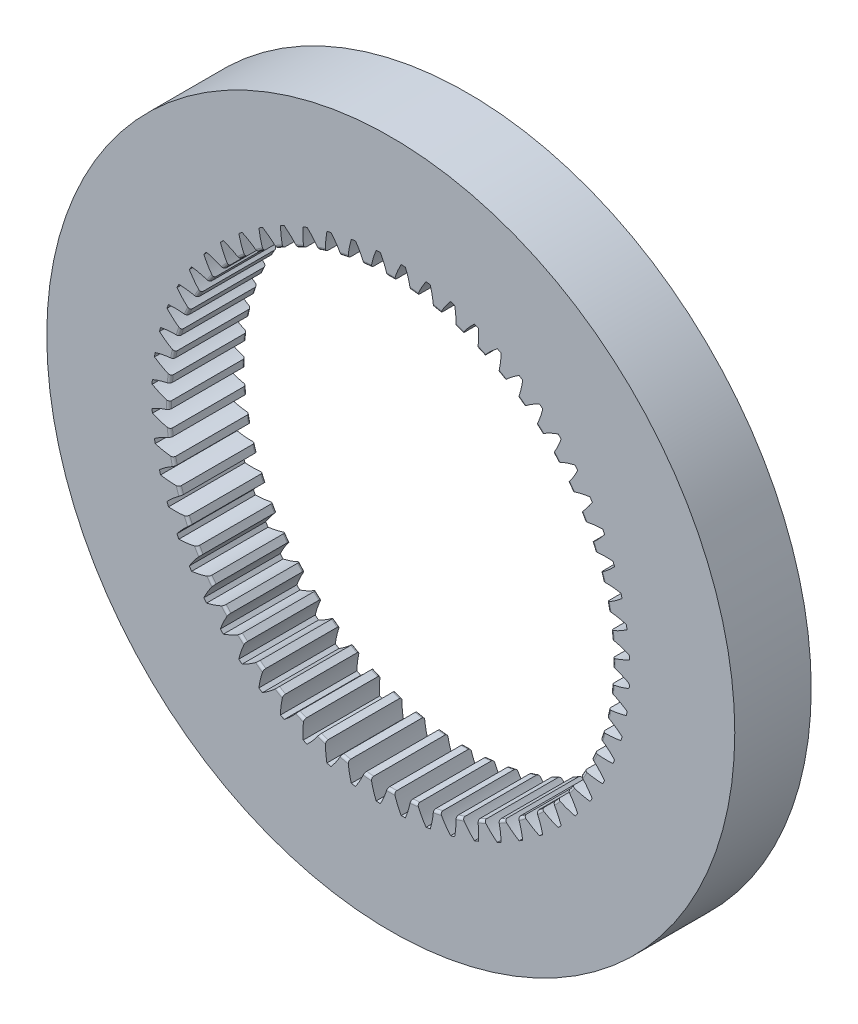
SolidWorks part; units mm, degrees
ref_plane "Front Plane" through (0, 0, 0) normal (0, 0, 1) x (1, 0, 0)
ref_plane "Top Plane" through (0, 0, 0) normal (0, 1, 0) x (1, 0, 0)
ref_plane "Right Plane" through (0, 0, 0) normal (1, 0, 0) x (0, 0, -1)
sketch "Sketch1" plane through (0, 0, 0) normal (0, 0, 1) x (1, 0, 0)
  line L0 (0, 0) -> (0, 30) construction
  line L1 (-9.6418, 33.5093) -> (9.6418, 26.4907) construction
  circle A0 centre (0, 0) radius 31 construction
  circle A1 centre (0, 0) radius 31.25 construction
  circle A2 centre (0, 0) radius 30 construction
  circle A3 centre (0, 0) radius 28.1908 construction
  circle A4 centre (0, 0) radius 45 construction
  circle A5 centre (0, 0) radius 29 construction
  point P8 (0.5, 0)
  point P13 (30, 0)
  dimension "Outside Diameter" = 62.5
  dimension "Root Diameter" = 62
  dimension "Gear Pitch Diameter" = 60
  dimension "ID | Base Diameter" = 56.3816
  dimension "OD" = 90
  dimension "ID" = 58
  dimension "Pressure Angle" = 20
  dimension "Number of Teeth" = 60
  dimension "Module" = 1
sketch "Sketch2" plane through (0, 0, 0) normal (1, 0, 0) x (0, 0, -1)
  line L0 (-5, 0) -> (5, 0) construction
  dimension "Face Width" = 10
sketch "Sketch3" plane through (0, 0, 0) normal (0, 0, 1) x (1, 0, 0)
  circle A0 centre (0, 0) radius 45
  circle A1 centre (0, 0) radius 29 construction
  circle A2 centre (0, 0) radius 29
  circle A4 centre (0, 0) radius 45 construction
extrude "Boss-Extrude1" add sketch "Sketch3" against normal up to vertex (5 mm away) and the other way up to vertex (5 mm away) up to point (0, 0, -5) other way up to point (0, 0, 5)
fillet "Fillet1" radius 0.3355 2 edges at (29, 0, -5) (29, 0, 5)
sketch "Sketch4" plane through (0, 0, 0) normal (0, 0, 1) x (1, 0, 0)
  line L2 (0, 0) -> (28.189, -0.3179) construction
  line L3 (0, 0) -> (28.189, 0.3179) construction
  line L4 (0, 0) -> (28.0678, -2.6304) construction
  circle A4 centre (0, 0) radius 28.1908 construction
  circle A5 centre (0, 0) radius 31.25 construction
  arc A7 (31.2205, -1.3573) -> (31.1914, -1.9136) centre (0, 0) cw
  arc A8 (28.189, -0.3179) -> (28.0678, -2.6304) centre (0, 0) cw
  spline S0 degree 4 poles (28.189, 0.3179) (28.1938, 0.318) (28.2071, 0.3184) (28.2324, 0.3198) (28.2736, 0.323) (28.3261, 0.3282) (28.3939, 0.3364) (28.4738, 0.3479) (28.5615, 0.3624) (28.6569, 0.3802) (28.7519, 0.3999) (28.8467, 0.4212) (28.941, 0.4439) (29.0552, 0.4733) (29.192, 0.511) (29.3517, 0.5588) (29.5326, 0.6173) (29.7167, 0.6815) (29.8976, 0.7486) (30.0801, 0.8207) (30.2564, 0.8936) (30.4393, 0.9739) (30.6079, 1.0502) (30.7965, 1.1408) (30.9486, 1.2153) (31.1487, 1.3189) (31.2668, 1.3817) (31.4048, 1.457) (31.4661, 1.4914) (31.5038, 1.5125) knots 0 0 0 0 0 0.005377 0.015084 0.028532 0.04661 0.064855 0.092111 0.119476 0.146842 0.174209 0.201575 0.228941 0.256307 0.307035 0.361767 0.4165 0.471232 0.525964 0.580697 0.635429 0.690161 0.744894 0.799626 0.854358 0.909091 0.954545 1 1 1 1 1 construction
  spline S1 degree 4 poles (28.189, 0.3179) (28.1938, 0.318) (28.2071, 0.3184) (28.2324, 0.3198) (28.2736, 0.323) (28.3261, 0.3282) (28.3939, 0.3364) (28.4738, 0.3479) (28.5615, 0.3624) (28.6569, 0.3802) (28.7519, 0.3999) (28.8467, 0.4212) (28.941, 0.4439) (29.0552, 0.4733) (29.192, 0.511) (29.3517, 0.5588) (29.5326, 0.6173) (29.7167, 0.6815) (29.8976, 0.7486) (30.0801, 0.8207) (30.2564, 0.8936) (30.4393, 0.9739) (30.6079, 1.0502) (30.7965, 1.1408) (30.9486, 1.2153) (31.1053, 1.2964) (31.1816, 1.3365) (31.2205, 1.3573) knots 0 0 0 0 0 0.005377 0.015084 0.028532 0.04661 0.064855 0.092111 0.119476 0.146842 0.174209 0.201575 0.228941 0.256307 0.307035 0.361767 0.4165 0.471232 0.525964 0.580697 0.635429 0.690161 0.744894 0.799626 0.854358 0.909091 0.909091 0.909091 0.909091 0.909091 construction
  spline S2 degree 4 poles (28.189, -0.3179) (28.1938, -0.318) (28.2071, -0.3184) (28.2324, -0.3198) (28.2736, -0.323) (28.3261, -0.3282) (28.3939, -0.3364) (28.4738, -0.3479) (28.5615, -0.3624) (28.6569, -0.3802) (28.7519, -0.3999) (28.8467, -0.4212) (28.941, -0.4439) (29.0552, -0.4733) (29.192, -0.511) (29.3517, -0.5588) (29.5326, -0.6173) (29.7167, -0.6815) (29.8976, -0.7486) (30.0801, -0.8207) (30.2564, -0.8936) (30.4393, -0.9739) (30.6079, -1.0502) (30.7965, -1.1408) (30.9486, -1.2153) (31.1487, -1.3189) (31.2668, -1.3817) (31.4048, -1.457) (31.4661, -1.4914) (31.5038, -1.5125) knots 0 0 0 0 0 0.005377 0.015084 0.028532 0.04661 0.064855 0.092111 0.119476 0.146842 0.174209 0.201575 0.228941 0.256307 0.307035 0.361767 0.4165 0.471232 0.525964 0.580697 0.635429 0.690161 0.744894 0.799626 0.854358 0.909091 0.954545 1 1 1 1 1 construction
  spline S3 degree 4 poles (28.189, -0.3179) (28.1938, -0.318) (28.2071, -0.3184) (28.2324, -0.3198) (28.2736, -0.323) (28.3261, -0.3282) (28.3939, -0.3364) (28.4738, -0.3479) (28.5615, -0.3624) (28.6569, -0.3802) (28.7519, -0.3999) (28.8467, -0.4212) (28.941, -0.4439) (29.0552, -0.4733) (29.192, -0.511) (29.3517, -0.5588) (29.5326, -0.6173) (29.7167, -0.6815) (29.8976, -0.7486) (30.0801, -0.8207) (30.2564, -0.8936) (30.4393, -0.9739) (30.6079, -1.0502) (30.7965, -1.1408) (30.9486, -1.2153) (31.1053, -1.2964) (31.1816, -1.3365) (31.2205, -1.3573) knots 0 0 0 0 0 0.005377 0.015084 0.028532 0.04661 0.064855 0.092111 0.119476 0.146842 0.174209 0.201575 0.228941 0.256307 0.307035 0.361767 0.4165 0.471232 0.525964 0.580697 0.635429 0.690161 0.744894 0.799626 0.854358 0.909091 0.909091 0.909091 0.909091 0.909091
  spline S4 degree 4 poles (28.0678, -2.6304) (28.0725, -2.6308) (28.0859, -2.6318) (28.1112, -2.633) (28.1525, -2.6342) (28.2052, -2.6345) (28.2736, -2.6334) (28.3542, -2.6304) (28.4429, -2.6251) (28.5396, -2.6173) (28.6362, -2.6077) (28.7327, -2.5964) (28.8289, -2.5837) (28.9455, -2.5664) (29.0855, -2.5432) (29.2493, -2.5124) (29.4354, -2.4731) (29.6251, -2.4284) (29.8121, -2.3807) (30.0011, -2.328) (30.1841, -2.2739) (30.3744, -2.2132) (30.5501, -2.1549) (30.747, -2.0846) (30.9061, -2.0264) (31.1159, -1.9443) (31.2399, -1.8942) (31.3851, -1.8337) (31.4496, -1.8059) (31.4893, -1.7888) knots 0 0 0 0 0 0.005377 0.015084 0.028532 0.04661 0.064855 0.092111 0.119476 0.146842 0.174209 0.201575 0.228941 0.256307 0.307035 0.361767 0.4165 0.471232 0.525964 0.580697 0.635429 0.690161 0.744894 0.799626 0.854358 0.909091 0.954545 1 1 1 1 1 construction
  spline S5 degree 4 poles (28.0678, -2.6304) (28.0725, -2.6308) (28.0859, -2.6318) (28.1112, -2.633) (28.1525, -2.6342) (28.2052, -2.6345) (28.2736, -2.6334) (28.3542, -2.6304) (28.4429, -2.6251) (28.5396, -2.6173) (28.6362, -2.6077) (28.7327, -2.5964) (28.8289, -2.5837) (28.9455, -2.5664) (29.0855, -2.5432) (29.2493, -2.5124) (29.4354, -2.4731) (29.6251, -2.4284) (29.8121, -2.3807) (30.0011, -2.328) (30.1841, -2.2739) (30.3744, -2.2132) (30.5501, -2.1549) (30.747, -2.0846) (30.9061, -2.0264) (31.0704, -1.9621) (31.1505, -1.9302) (31.1914, -1.9136) knots 0 0 0 0 0 0.005377 0.015084 0.028532 0.04661 0.064855 0.092111 0.119476 0.146842 0.174209 0.201575 0.228941 0.256307 0.307035 0.361767 0.4165 0.471232 0.525964 0.580697 0.635429 0.690161 0.744894 0.799626 0.854358 0.909091 0.909091 0.909091 0.909091 0.909091
  point P11 (0, 0)
  dimension "D1" = 6
extrude "Cut-Extrude1" cut sketch "Sketch4" against normal through all both and the other way through all
fillet "Fillet2" radius 0.3355 2 edges at (31.1914, -1.9136, 0) (31.2205, -1.3573, 0)
pattern_circular "CirPattern1" count 60 over 360 about axis through (0, 0, 5) along (0, 0, -1) of "Cut-Extrude1"
equation "\"Root Diameter@Sketch1\"=\"Root Diameter\""
equation "\"Outside Diameter@Sketch1\" = \"Outside Diameter\""
equation "\"D1@CirPattern1\"=\"Number of Teeth\""
equation "\"Diametral Pitch\"= 1 / \"Module\""
equation "\"Number of Teeth\"= 60"
equation "\"Pressure Angle\"=20"
equation "\"Pitch Diameter\"= \"Number of Teeth\" / \"Diametral Pitch\""
equation "\"Base Diameter\"= \"Pitch Diameter\" * cos ( \"Pressure Angle\" )"
equation "\"Outside Diameter\"= \"Pitch Diameter\" + ( 2 * \"Dedendum\" )"
equation "\"Dedendum\"= 1.25 / \"Diametral Pitch\""
equation "\"Root Diameter\"= \"Pitch Diameter\" + ( 2 * \"Addendum\" )"
equation "\"Pitch Angle\"= 360deg / \"Number of Teeth\""
equation "\"Alpha\"= sqr ( \"Pitch Diameter\" ^ 2 - \"Base Diameter\" ^ 2 ) / \"Base Diameter\" * 180 / PI - \"Pressure Angle\""
equation "\"Beta\"= ( \"Pitch Angle\" / 4 - \"Alpha\" )"
equation "\"Phi\"= sqr ( ( \"Outside Diameter\" / 2 ) ^ 2 - ( \"Base Diameter\" / 2 ) ^ 2 ) / ( \"Base Diameter\" / 2 )"
equation "\"Addendum\"= 1 / \"Diametral Pitch\""
equation "\"WorkingDepth\"= 2 / \"Diametral Pitch\""
equation "\"WholeDepth\"= 2.25 / \"Diametral Pitch\""
equation "\"Clearance\"= 0.25 / \"Diametral Pitch\""
equation "\"ToothThickness\"= ( pi * 2 ) / \"Diametral Pitch\""
equation "\"CircularPitch\"= pi / \"Diametral Pitch\""
equation "\"Number of Teeth@Sketch1\"=\"Number of Teeth\""
equation "\"Module@Sketch1\"=\"Module\""
equation "\"Pressure Angle@Sketch1\"=\"Pressure Angle\""
equation "\"Gear Pitch Diameter@Sketch1\"=\"Pitch Diameter\""
equation "\"ID | Base Diameter@Sketch1\" = \"Base Diameter\""
equation "\"Fillet\"= \"Clearance\" * cos ( \"Pressure Angle\" ) * tan ( ( 90 + \"Pressure Angle\" ) / 2 )"
equation "\"D1@Sketch4\"=360/\"Number of Teeth\""
equation "\"D1@Fillet1\" = \"Fillet\""
equation "\"D1@Fillet2\"=\"Fillet\""
equation "\"Module\"= 1"
